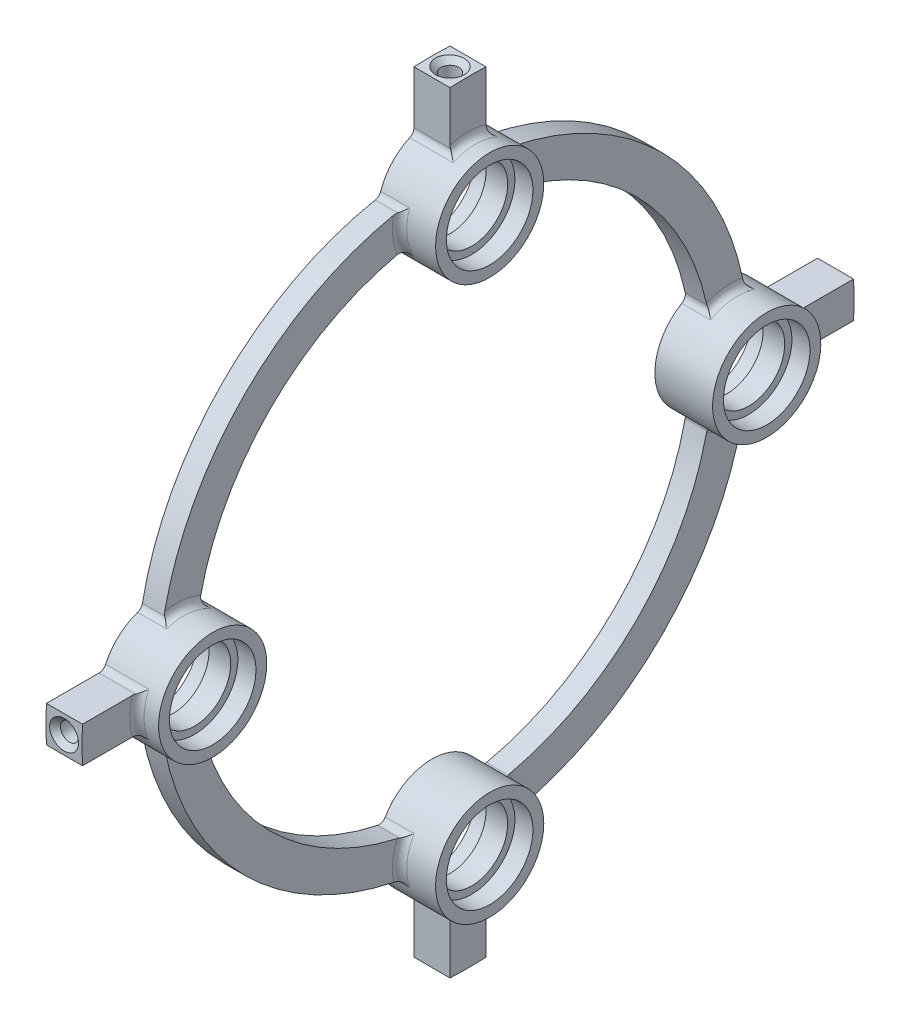
SolidWorks part; units mm, degrees
ref_plane "Спереди" through (0, 0, 0) normal (0, 0, 1) x (1, 0, 0)
ref_plane "Сверху" through (0, 0, 0) normal (0, 1, 0) x (1, 0, 0)
ref_plane "Справа" through (0, 0, 0) normal (1, 0, 0) x (0, 0, -1)
sketch "Эскиз3" plane through (0, 0, 0) normal (1, 0, 0) x (0, 0, -1)
  circle A0 centre (0, 0) radius 38.4 construction
  dimension "D1" = 76.8
sketch "Эскиз1" plane through (0, 0, 0) normal (1, 0, 0) x (0, 0, -1)
  line L0 (40.9, 0) -> (35.9, 0) construction
  circle A3 centre (0, 0) radius 40.9
  circle A4 centre (0, 0) radius 35.9
  circle A5 centre (0, 0) radius 38.4 construction
  point P9 (38.4, 0)
  dimension "D1" = 5
extrude "Бобышка-Вытянуть1" add sketch "Эскиз1" along normal blind 3
sketch "Эскиз2" plane through (0, 0, 0) normal (-1, 0, 0) x (0, 0, 1)
  circle A0 centre (0, 38.4) radius 7.5
  circle A1 centre (0, 0) radius 38.4 construction
  dimension "D1" = 15
extrude "Бобышка-Вытянуть2" add sketch "Эскиз2" against normal blind 8
sketch "Эскиз4" plane through (0, 0, 0) normal (-1, 0, 0) x (0, 0, 1)
  circle A0 centre (0, 38.4) radius 5
  dimension "D1" = 10
extrude "Вырез-Вытянуть1" cut sketch "Эскиз4" against normal through all
sketch "Эскиз5" plane through (0, 0, 0) normal (-1, 0, 0) x (0, 0, 1)
  circle A0 centre (0, 38.4) radius 6
  dimension "D1" = 12
extrude "Вырез-Вытянуть2" cut sketch "Эскиз5" against normal blind 2.5
sketch "Эскиз6" plane through (8, 0, 0) normal (1, 0, 0) x (0, 0, -1)
  circle A0 centre (0, 38.4) radius 6
  dimension "D1" = 12
extrude "Вырез-Вытянуть3" cut sketch "Эскиз6" against normal blind 2.5
sketch "Эскиз7" plane through (0, 0, 0) normal (-1, 0, 0) x (0, 0, 1)
  line L0 (0, 0) -> (0, 53.5) construction
  line L1 (-2.5, 53.4416) -> (-2.5, 45.4711)
  line L2 (2.5, 53.4416) -> (2.5, 45.4711)
  circle A0 centre (0, 0) radius 53.5 construction
  arc A1 (7.2685, 40.249) -> (-7.2685, 40.249) centre (0, 38.4) ccw construction
  arc A2 (-2.5, 53.4416) -> (2.5, 53.4416) centre (0, 0) cw
  arc A3 (-2.5, 45.4711) -> (2.5, 45.4711) centre (0, 38.4) cw
  dimension "D1" = 107
  dimension "D2" = 5
extrude "Бобышка-Вытянуть3" add sketch "Эскиз7" against normal blind 5
fillet "Скругление1" radius 1 9 edges at (3, 37.7091, 7.4681) (3, 37.7091, -7.4681) (1.5, 35.249, -6.8059) (1.5, 35.249, 6.8059) (1.5, 40.249, 7.2685) (1.5, 40.249, -7.2685) (5, 45.9, 0) (2.5, 45.4711, 2.5) (2.5, 45.4711, -2.5)
hole_wizard "Отверстие обработанное метчиком M31" positions "Трехмерный эскиз1" profile "Эскиз8" tap size "M3" standard "ISO"
sketch3d "Трехмерный эскиз1"
  line L2 (2.5, 53.4416, 2.5) -> (2.5, 53.4416, 0) construction
  line L3 (5, 53.4416, 2.5) -> (0, 53.4416, 2.5) construction
  line L7 (2.5, 53.4416, 0) -> (2.5, 53.5, 0) construction
  line L12 (0, 53.4416, 2.5) -> (0, 53.4416, -2.5) construction
  line L13 (2.5, 53.4416, 0) -> (0, 53.4416, 0) construction
  point P0 (2.5, 53.5, 0)
  point P50 (0, 53.4416, 0)
sketch "Эскиз8" plane through (2.5, 53.5, 0) normal (1, 0, 0) x (0, 0, 1)
  line L0 (0, 0) -> (0, 7.7511)
  line L1 (0, 7.7511) -> (1.25, 7)
  line L2 (1.25, 7) -> (1.25, 0.75)
  line L3 (1.25, 0.75) -> (2, 0)
  line L5 (2, 0) -> (0, 0)
  line L6 (-1.25, 0.75) -> (-2, 0) construction
  line L10 (0, 7.7511) -> (-1.25, 7) construction
  line L11 (0, -6.35) -> (0, 107.95) construction
  dimension "Диаметр сверла" = 2.5
  dimension "Глубина сверла" = 7
  dimension "Диаметр передней зенковки" = 4
  dimension "Угол передней зенковки" = 90
  dimension "Угол заточки сверла" = 118
cosmetic thread "Отверстие резьбы1" parameters "D1"=6, "D2"=3
pattern_circular "Круговой массив1" count 4 over 360 about axis through (3, 0, 0) along (-1, 0, 0) of "Бобышка-Вытянуть2", "Вырез-Вытянуть1", "Вырез-Вытянуть2", "Вырез-Вытянуть3", "Бобышка-Вытянуть3", "Скругление1", "Отверстие обработанное метчиком M31"
